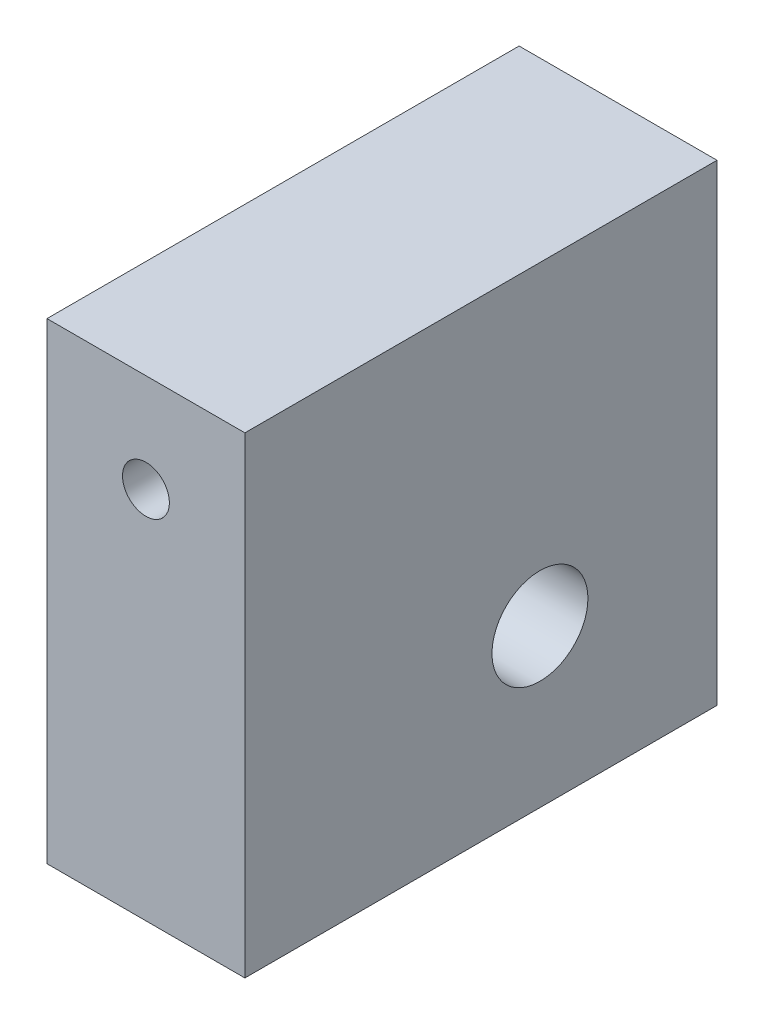
SolidWorks part; units mm, degrees
material "6061-T4 (SS)"
ref_plane "Front Plane" through (0, 0, 0) normal (0, 0, 1) x (1, 0, 0)
ref_plane "Top Plane" through (0, 0, 0) normal (0, 1, 0) x (1, 0, 0)
ref_plane "Right Plane" through (0, 0, 0) normal (1, 0, 0) x (0, 0, -1)
sketch "Sketch1" plane through (0, 0, 0) normal (1, 0, 0) x (0, 0, -1)
  line L1 (0, 0) -> (12, 0)
  line L2 (0, 0) -> (0, 12)
  line L3 (0, 12) -> (12, 12)
  line L4 (12, 0) -> (12, 12)
  dimension "D1" = 12
  dimension "D2" = 12
extrude "Boss-Extrude1" add sketch "Sketch1" along normal blind 5.03
sketch "Sketch2" plane through (5.03, 0, 0) normal (1, 0, 0) x (0, 0, -1)
  line L0 (8.1944, 12) -> (8.1944, 6.542) construction
  line L1 (12, 12) -> (0, 12) construction
  line L2 (0, 12) -> (0, 0) construction
  point P2 (7.5, 4)
  point P9 (8.1944, 6.542)
  dimension "D1" = 8.1944
  dimension "D2" = 5.458
sketch "Sketch3" plane through (0, 0, 0) normal (0, 0, 1) x (1, 0, 0)
  line L0 (2.515, 12) -> (2.515, 9.5) construction
  line L1 (5.03, 12) -> (0, 12) construction
  dimension "D1" = 2.5
hole_wizard "Tap Drill for #0-80 Tap1" positions "Sketch5" profile "Sketch4" hole size "#0-80" standard "ANSI Inch"
sketch "Sketch5" plane through (0, 0, 0) normal (0, 0, 1) x (1, 0, 0)
  point P0 (2.515, 9.5)
sketch "Sketch4" plane through (2.515, 9.5, 0) normal (1, 0, 0) x (0, -1, 0)
  line L0 (0, 0) -> (0, 4.3579)
  line L1 (0, 4.3579) -> (0.5956, 4)
  line L2 (0.5956, 4) -> (0.5956, 0)
  line L5 (0.5956, 0) -> (0, 0)
  line L10 (0, 4.3579) -> (-0.5956, 4) construction
  line L11 (0, -6.35) -> (0, 107.95) construction
  dimension "Hole Dia." = 1.1913
  dimension "Hole Depth" = 4
  dimension "Drill Angle" = 118
hole_wizard "#2 Clearance Hole1" positions "Sketch6" profile "Sketch7" hole size "#2" standard "ANSI Inch" end condition through all
sketch "Sketch6" plane through (5.03, 0, 0) normal (1, 0, 0) x (0, 0, -1)
  point P5 (7.5, 4)
sketch "Sketch7" plane through (5.03, 4, -7.5) normal (0, 1, 0) x (0, 0, -1)
  line L0 (0, 0) -> (0, 5.03)
  line L1 (0, 5.03) -> (1.2192, 5.03)
  line L2 (1.2192, 5.03) -> (1.2192, 0)
  line L5 (1.2192, 0) -> (0, 0)
  line L11 (0, -6.35) -> (0, 107.95) construction
  dimension "Thru Hole Dia." = 2.4384
  dimension "Thru Hole Depth" = 5.03
